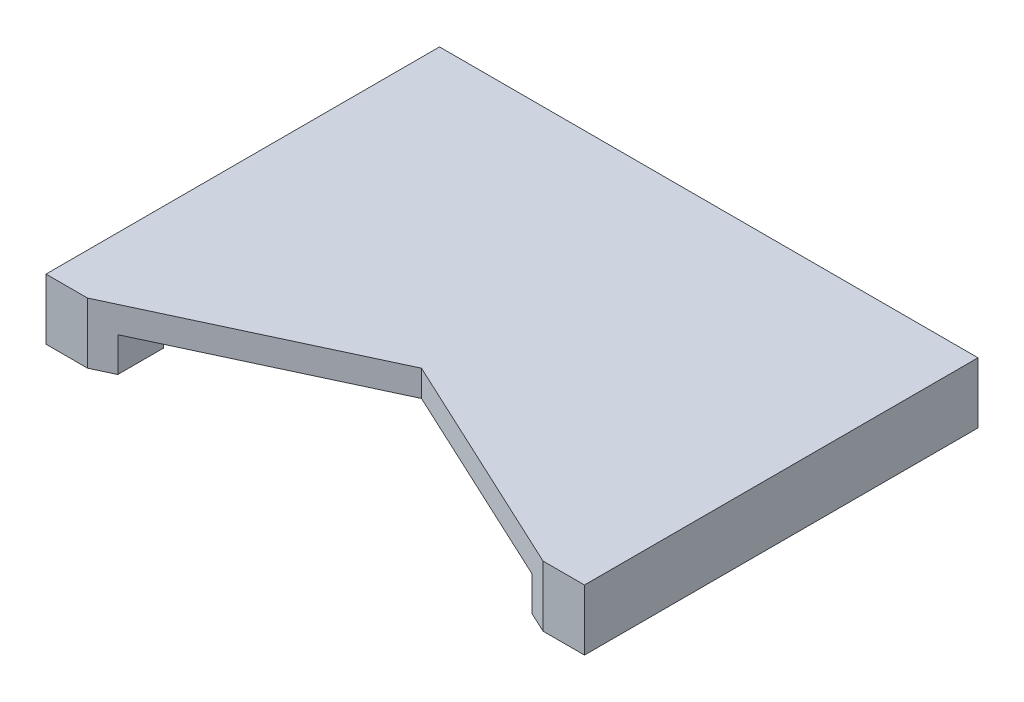
SolidWorks part; units mm, degrees
ref_plane "Front Plane" through (0, 0, 0) normal (0, 0, 1) x (1, 0, 0)
ref_plane "Top Plane" through (0, 0, 0) normal (0, 1, 0) x (1, 0, 0)
ref_plane "Right Plane" through (0, 0, 0) normal (1, 0, 0) x (0, 0, -1)
sketch "Sketch1" plane through (0, 0, 0) normal (0, 1, 0) x (1, 0, 0)
  line L1 (0, 0) -> (78, 0)
  line L2 (0, 0) -> (0, 57)
  line L3 (0, 57) -> (78, 57)
  line L4 (78, 0) -> (78, 57)
  dimension "D1" = 57
  dimension "D2" = 78
extrude "Boss-Extrude1" add sketch "Sketch1" along normal blind 8.8
sketch "Sketch2" plane through (0, 0, 0) normal (0, -1, 0) x (1, 0, 0)
  line L0 (78, -57) -> (0, -57) construction
  line L1 (6, -57) -> (72, -57)
  line L2 (6, -57) -> (6, -8)
  line L3 (6, -8) -> (72, -8)
  line L4 (72, -57) -> (72, -8)
  line L5 (0, -57) -> (0, 0) construction
  line L6 (78, 0) -> (78, -57) construction
  dimension "D1" = 6
  dimension "D2" = 6
  dimension "D3" = 49
extrude "Cut-Extrude1" cut sketch "Sketch2" against normal blind 5
sketch "Sketch3" plane through (0, 0, 0) normal (0, -1, 0) x (1, 0, 0)
  line L0 (72, -8) -> (6, -8) construction
  line L1 (9, -8) -> (69, -8)
  line L2 (9, -8) -> (9, 0)
  line L3 (9, 0) -> (69, 0)
  line L4 (69, -8) -> (69, 0)
  line L5 (0, 0) -> (78, 0) construction
  line L6 (0, -57) -> (0, 0) construction
  line L7 (78, 0) -> (78, -57) construction
  dimension "D1" = 9
  dimension "D2" = 9
extrude "Cut-Extrude2" cut sketch "Sketch3" against normal up to surface (5 mm away) up to face at (39, 5, -32.5)
sketch "Sketch4" plane through (0, 8.8, 0) normal (0, 1, 0) x (1, 0, 0)
  line L0 (0, 0) -> (78, 0) construction
  line L1 (6, 0) -> (39, 15.3882)
  line L2 (39, 15.3882) -> (72, 0)
  line L3 (39, 15.3882) -> (39, 57) construction
  line L4 (72, 0) -> (6, 0)
  line L5 (78, 57) -> (0, 57) construction
  dimension "D1" = 130
  dimension "D2" = 6
extrude "Cut-Extrude3" cut sketch "Sketch4" against normal up to next
